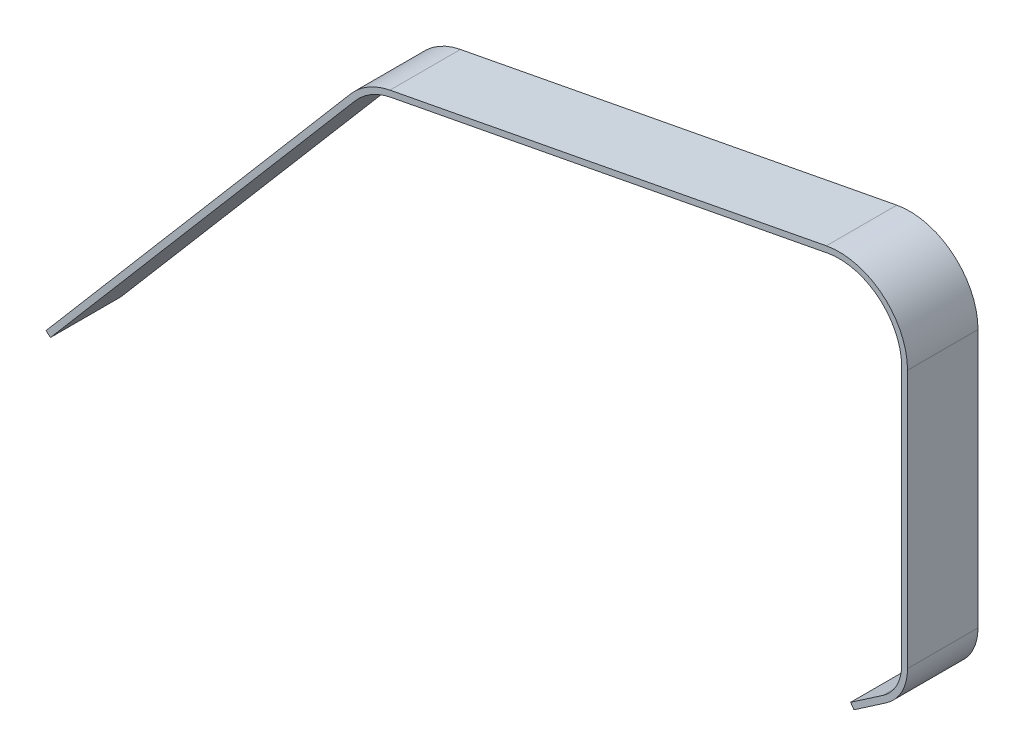
SolidWorks part; units mm, degrees
ref_plane "Front Plane" through (0, 0, 0) normal (0, 0, 1) x (1, 0, 0)
ref_plane "Top Plane" through (0, 0, 0) normal (0, 1, 0) x (1, 0, 0)
ref_plane "Right Plane" through (0, 0, 0) normal (1, 0, 0) x (0, 0, -1)
sketch "Sketch1" plane through (0, 0, 0) normal (0, 0, 1) x (1, 0, 0)
  line L0 (-6.9353, 36.3108) -> (229.0527, 81.3841)
  line L1 (0, 0) -> (17.6031, 3.3622) construction
  line L2 (229.0527, 81.3841) -> (236.3186, 43.342) construction
  line L6 (-6.9353, 36.3108) -> (0, 0) construction
  line L9 (271.9391, -94.6575) -> (246.5391, -94.6575) construction
  line L11 (242.1807, -125.8125) -> (243.9749, -128.432)
  line L12 (272.9551, 45.0733) -> (272.9551, -94.6267)
  line L13 (262.0187, -117.2578) -> (258.1196, -111.5652) construction
  line L14 (243.9749, -128.432) -> (261.4664, -116.4516)
  line L15 (-28.1294, 23.9856) -> (-26.1434, 22.2922) construction
  line L19 (-28.1294, 23.9856) -> (-192.9335, -169.2904)
  line L20 (-192.9335, -169.2904) -> (-190.5176, -171.3504)
  line L21 (272.9551, -94.6267) -> (267.1112, -94.6575) construction
  line L22 (242.1807, -125.8125) -> (259.6723, -113.8321)
  line L23 (272.9551, 45.0733) -> (252.5102, 45.0733) construction
  line L24 (269.7801, -94.6575) -> (269.7801, 45.0733)
  line L25 (229.6483, 78.2655) -> (-6.3397, 33.1922)
  line L26 (-28.1294, 23.9856) -> (-24.6287, 21.1399) construction
  line L27 (-25.665, 21.9823) -> (-190.5176, -171.3504)
  arc A0 (-28.1294, 23.9856) -> (-6.9353, 36.3108) centre (0, 0) cw
  arc A1 (229.0527, 81.3841) -> (272.9551, 45.0733) centre (235.988, 45.0733) cw
  arc A5 (272.9551, -94.6267) -> (261.4664, -116.4516) centre (246.5391, -94.6575) cw
  arc A6 (259.6723, -113.8321) -> (269.7801, -94.6575) centre (246.5391, -94.6575) ccw
  arc A7 (269.7801, 45.0733) -> (229.6483, 78.2655) centre (235.988, 45.0733) ccw
  arc A8 (-6.3397, 33.1922) -> (-25.665, 21.9823) centre (0, 0) ccw
  dimension "D5" = 36.9672
  dimension "D8" = 26.416
  dimension "D1" = 254
  dimension "D2" = 3.175
  dimension "D7" = 3.175
  dimension "D9" = 139.7
extrude "Boss-Extrude1" add sketch "Sketch1" along normal blind 38.1 contours A1 L0 A0 region at (111.1582, 58.3265, 0)
